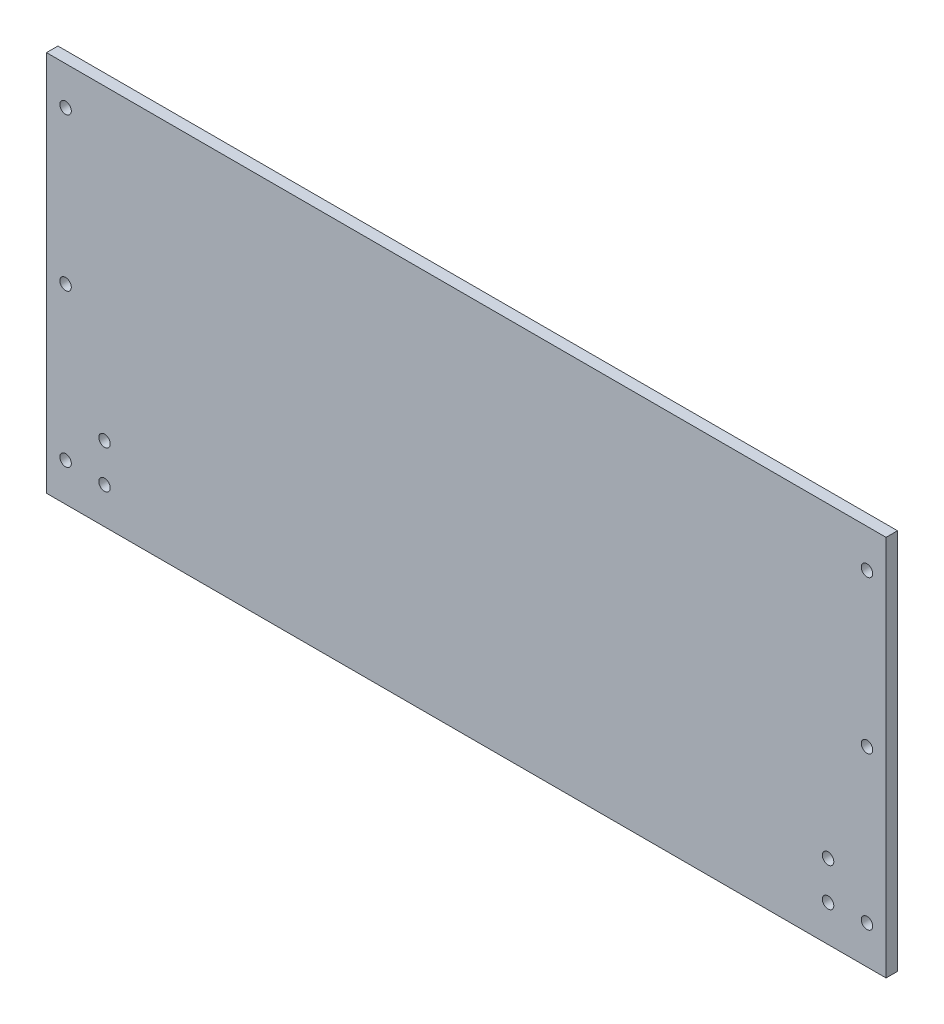
SolidWorks part; units mm, degrees
ref_plane "Plan de face" through (0, 0, 0) normal (0, 0, 1) x (1, 0, 0)
ref_plane "Plan de dessus" through (0, 0, 0) normal (0, 1, 0) x (1, 0, 0)
ref_plane "Plan de droite" through (0, 0, 0) normal (1, 0, 0) x (0, 0, -1)
sketch "Esquisse1" plane through (0, 0, 0) normal (0, 0, 1) x (1, 0, 0)
  line L0 (-105, -50) -> (-105, 50) construction
  line L1 (110, -50) -> (-110, -50)
  line L2 (110, -50) -> (110, 50)
  line L3 (110, 50) -> (-110, 50)
  line L4 (-110, -50) -> (-110, 50)
  line L5 (110, -50) -> (-110, 50) construction
  line L6 (110, 50) -> (-110, -50) construction
  line L7 (0, 50) -> (0, -50) construction
  circle A0 centre (-105, -40) radius 1.5
  circle A1 centre (-105, 0) radius 1.5
  circle A2 centre (-105, 40) radius 1.5
  circle A3 centre (105, 40) radius 1.5
  circle A4 centre (105, 0) radius 1.5
  circle A5 centre (105, -40) radius 1.5
  circle A6 centre (-94.8, -30.4553) radius 1.5
  circle A10 centre (-94.8, -40.4553) radius 1.5
  circle A11 centre (94.8, -40.4553) radius 1.5
  circle A12 centre (94.8, -30.4553) radius 1.5
  point P0 (0, 0)
  dimension "D4" = 3
  dimension "D8" = 3
  dimension "D9" = 3
  dimension "D1" = 220
  dimension "D2" = 100
  dimension "D3" = 5
  dimension "D5" = 10
  dimension "D7" = 10
  dimension "D6" = 3
extrude "Boss.-Extru.1" add sketch "Esquisse1" along normal blind 3
